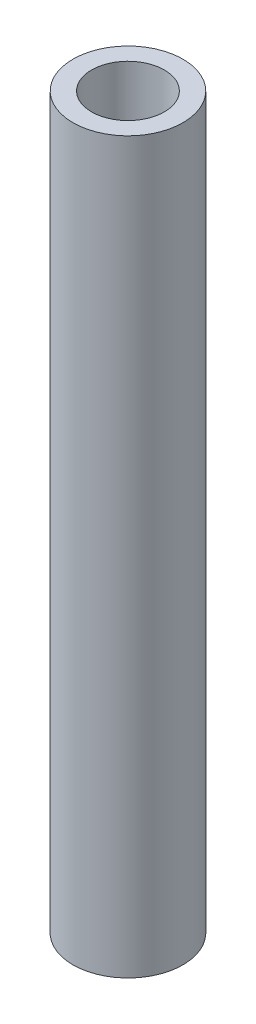
SolidWorks part; units mm, degrees
material "ABS"
ref_plane "Front Plane" through (0, 0, 0) normal (0, 0, 1) x (1, 0, 0)
ref_plane "Top Plane" through (0, 0, 0) normal (0, 1, 0) x (1, 0, 0)
ref_plane "Right Plane" through (0, 0, 0) normal (1, 0, 0) x (0, 0, -1)
sketch "Sketch1" plane through (0, 0, 0) normal (0, 1, 0) x (1, 0, 0)
  circle A0 centre (0, 0) radius 4.425
  circle A1 centre (0, 0) radius 2.925
  dimension "D1" = 8.85
  dimension "D2" = 1.5
extrude "Boss-Extrude1" add sketch "Sketch1" against normal up to surface (58.65 mm away)
